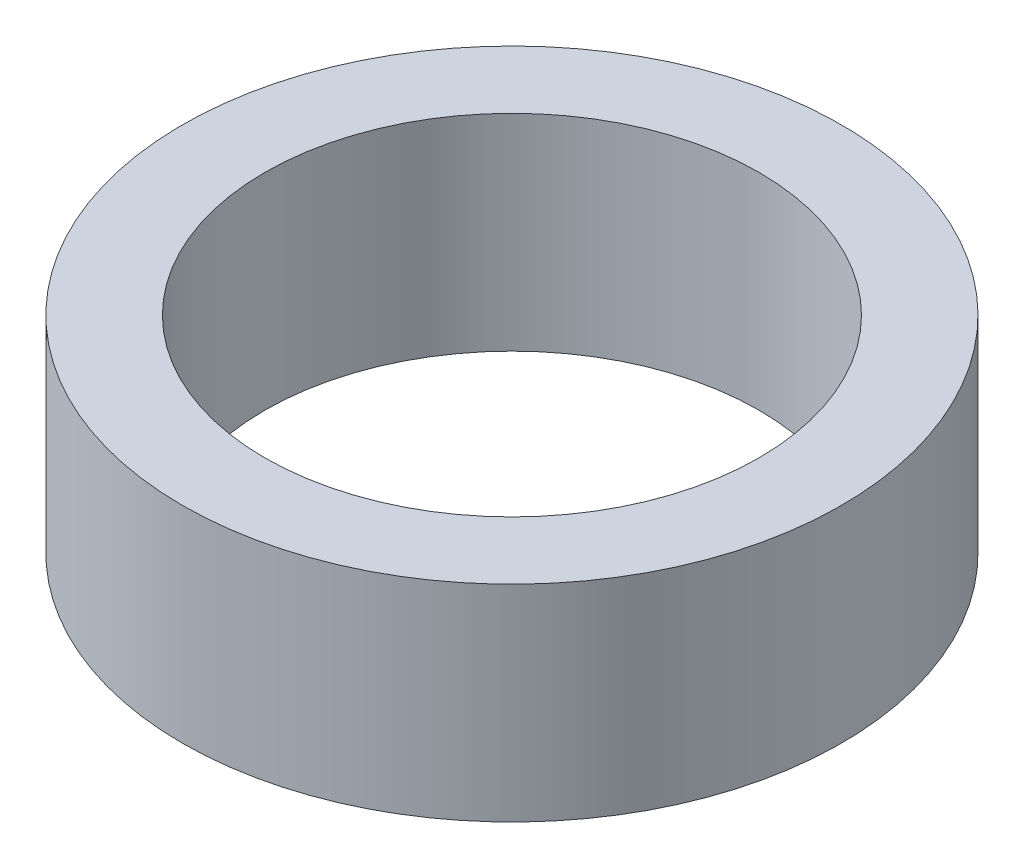
SolidWorks part; units mm, degrees
ref_plane "Front Plane" through (0, 0, 0) normal (0, 0, 1) x (1, 0, 0)
ref_plane "Top Plane" through (0, 0, 0) normal (0, 1, 0) x (1, 0, 0)
ref_plane "Right Plane" through (0, 0, 0) normal (1, 0, 0) x (0, 0, -1)
sketch "Sketch1" plane through (0, 0, 0) normal (0, 1, 0) x (1, 0, 0)
  circle A0 centre (0, 0) radius 40
  dimension "FLANGE_OD" = 80
extrude "Boss-Extrude1" add sketch "Sketch1" along normal blind 25
sketch "Sketch2" plane through (0, 0, 0) normal (0, 1, 0) x (1, 0, 0)
  circle A0 centre (0, 0) radius 30
  dimension "BORE_D" = 60
extrude "Cut-Extrude1" cut sketch "Sketch2" along normal through all
sketch "Sketch3" plane through (0, 25, 0) normal (0, 1, 0) x (1, 0, 0)
  circle A0 centre (0, 0) radius 18.1504 construction
  circle A1 centre (-18.1504, 0) radius 1.6617
  dimension "BOLT_D" = 3.3234
  dimension "BOLT_PCD" = 36.3008
extrude "Cut-Extrude2" cut sketch "Sketch3" against normal blind 24.9899 rebuild error yes
pattern_circular "CirPattern1" count 4 over 360 rebuild error yes
